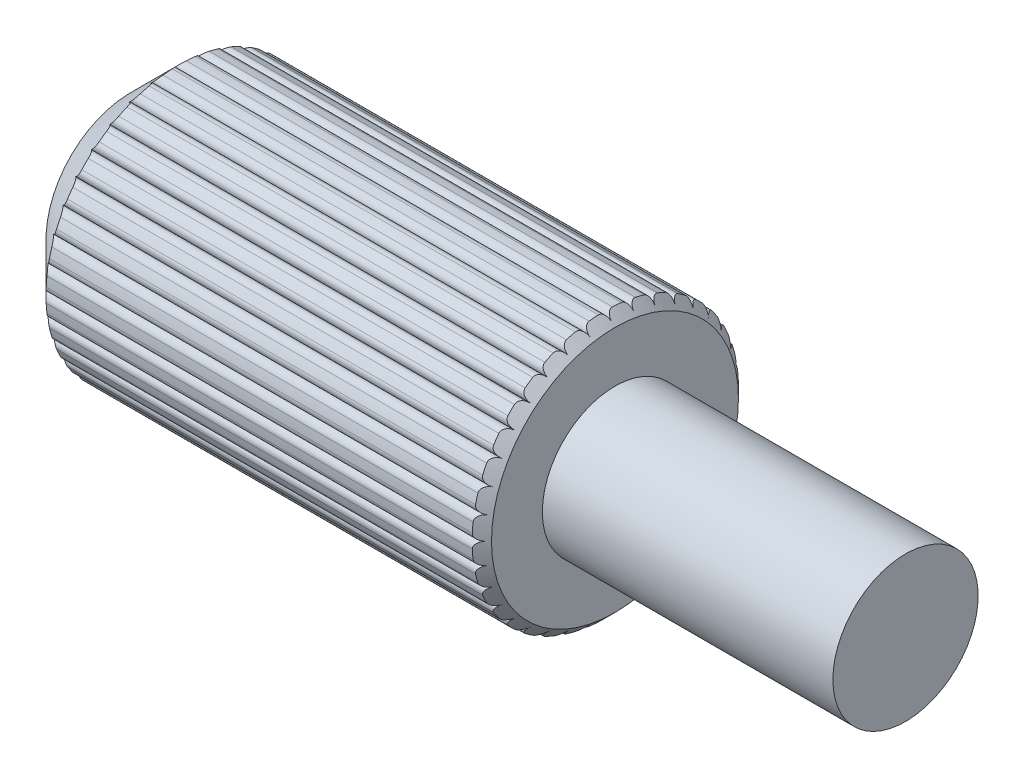
SolidWorks part; units mm, degrees
note: '?' marks a value the reader was unsure of.
ref_plane "前视基准面" through (0, 0, 0) normal (0, 0, 1) x (1, 0, 0)
ref_plane "上视基准面" through (0, 0, 0) normal (0, 1, 0) x (1, 0, 0)
ref_plane "右视基准面" through (0, 0, 0) normal (1, 0, 0) x (0, 0, -1)
sketch "草图1" plane through (0, 0, 0) normal (0, 0, 1) x (1, 0, 0)
  line L0 (0, 3.8245) -> (0, -3.9612) construction
  line L1 (0, 0) -> (10.7598, 0)
  point P5 (3, 0)
  point P6 (6, 0)
  point P7 (0.5, 0)
  point P8 (10, 0)
  point P9 (5.5, 0)
  dimension "M" = 3
  dimension "L" = 6
  dimension "P" = 0.5
  dimension "D" = 5.5
  dimension "K" = 10
sketch "草图2" plane through (0, 0, 0) normal (0, 0, 1) x (1, 0, 0)
  line L0 (-1.1477, 0) -> (16.1626, 0) construction
  line L1 (0, 3.398) -> (0, -3.4434) construction
  line L2 (0, 0) -> (0, 2.75)
  line L3 (0, 2.75) -> (10, 2.75)
  line L4 (10, 2.75) -> (10, 1.5)
  line L5 (10, 1.5) -> (16, 1.5)
  line L6 (16, 1.5) -> (16, 0)
  line L7 (16, 0) -> (0, 0)
  dimension "D1" = 5.5
  dimension "D2" = 10
  dimension "D3" = 6
  dimension "D4" = 3
revolve "旋转1" add sketch "草图2" angle 360 about L0
cosmetic thread "装饰螺纹线1" parameters "D2"=2.5
chamfer "倒角1" distance 1 angle 45 1 edges at (0, 0, 2.75)
chamfer "倒角2" distance 0.2 angle 45 1 edges at (10, 0, 2.75)
sketch "草图3" plane through (0, 0, 0) normal (-1, 0, 0) x (0, 0, 1)
  line L0 (0, 3.4573) -> (0, -3.2149) construction
  circle A1 centre (0, 0) radius 2.75 construction
  arc A2 (0.1447, 2.7462) -> (-0.1447, 2.7462) centre (0, 0) ccw
  arc A3 (0, 2.6089) -> (-0.1447, 2.7462) centre (-0.1375, 2.6089) ccw
  arc A4 (0, 2.6089) -> (0.1447, 2.7462) centre (0.1375, 2.6089) cw
  dimension "D1" = 0.275
extrude "切除-拉伸2" cut sketch "草图3" against normal up to next
ref_axis "基准轴1" through (9.8, 0, 0) along (-1, 0, 0)?
pattern_circular "阵列(圆周)2" count 36 over 360 about axis through (0, 0, 0) along (1, 0, 0) of "切除-拉伸2"
equation "\"D1@草图2\"=\"D@草图1\""
equation "\"D2@草图2\"=\"K@草图1\""
equation "\"D3@草图2\"=\"L@草图1\""
equation "\"D4@草图2\"=\"M@草图1\""
equation "\"D2@装饰螺纹线1\"=\"M@草图1\"-\"P@草图1\""
equation "\"D1@草图3\"=\"D@草图1\"*0.05"
